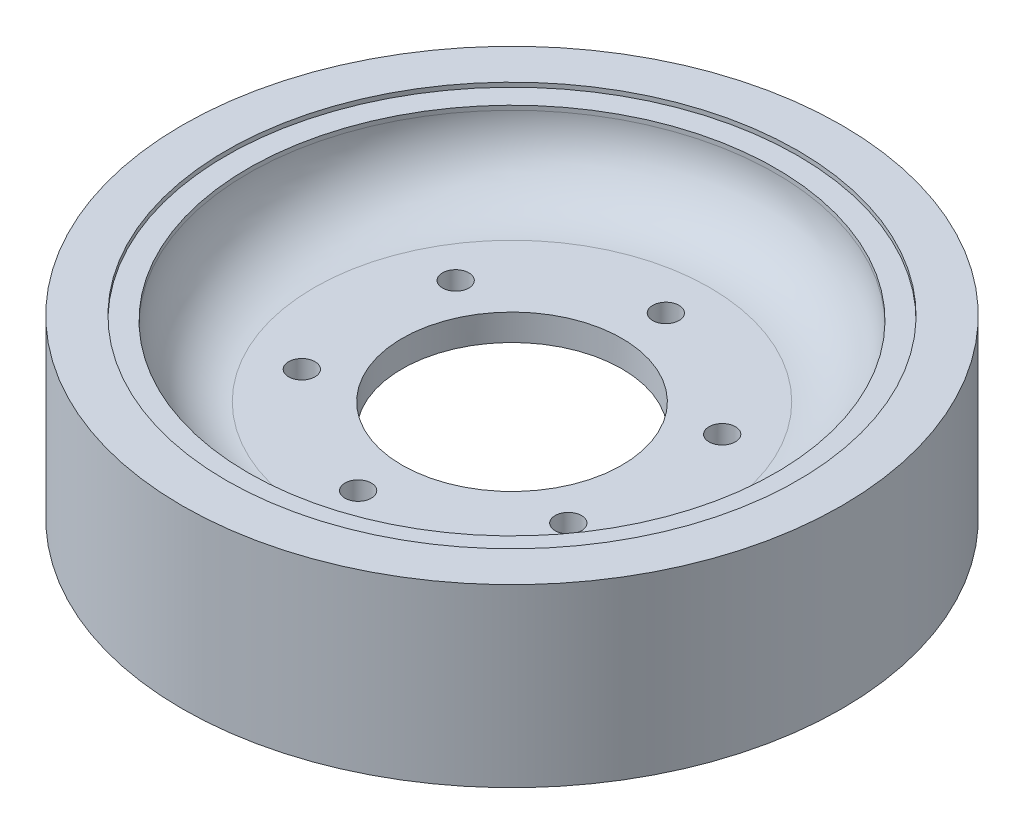
SolidWorks part; units mm, degrees
ref_plane "Front Plane" through (0, 0, 0) normal (0, 0, 1) x (1, 0, 0)
ref_plane "Top Plane" through (0, 0, 0) normal (0, 1, 0) x (1, 0, 0)
ref_plane "Right Plane" through (0, 0, 0) normal (1, 0, 0) x (0, 0, -1)
sketch "Sketch1" plane through (0, 0, 0) normal (0, 1, 0) x (1, 0, 0)
  circle A0 centre (0, 0) radius 75
  dimension "D1" = 150
extrude "Boss-Extrude1" add sketch "Sketch1" along normal blind 40
sketch "Sketch2" plane through (0, 40, 0) normal (0, 1, 0) x (1, 0, 0)
  circle A0 centre (0, 0) radius 60
  dimension "D1" = 120
extrude "Cut-Extrude1" cut sketch "Sketch2" against normal blind 17
sketch "Sketch3" plane through (0, 23, 0) normal (0, 1, 0) x (1, 0, 0)
  circle A0 centre (0, 0) radius 25
  dimension "D1" = 50
extrude "Cut-Extrude2" cut sketch "Sketch3" against normal through all
sketch "Sketch4" plane through (0, 23, 0) normal (0, 1, 0) x (1, 0, 0)
  circle A0 centre (0, 0) radius 35 construction
  circle A1 centre (0, 35) radius 3
  circle A2 centre (30.3109, 17.5) radius 3
  circle A3 centre (30.3109, -17.5) radius 3
  circle A4 centre (0, -35) radius 3
  circle A5 centre (-30.3109, -17.5) radius 3
  circle A6 centre (-30.3109, 17.5) radius 3
  point P17 (0, 0)
  dimension "D1" = 70
  dimension "D2" = 6
  dimension "D3" = 6
extrude "Cut-Extrude3" cut sketch "Sketch4" against normal through all
sketch "Sketch6" plane through (0, 0, 0) normal (0, -1, 0) x (1, 0, 0)
  circle A0 centre (0, 0) radius 60
  dimension "D1" = 120
extrude "Cut-Extrude4" cut sketch "Sketch6" against normal blind 17
sketch "Sketch7" plane through (0, 0, 0) normal (0, -1, 0) x (1, 0, 0)
  circle A0 centre (0, 0) radius 65
  dimension "D1" = 130
extrude "Cut-Extrude5" cut sketch "Sketch7" against normal blind 1
sketch "Sketch8" plane through (0, 40, 0) normal (0, 1, 0) x (1, 0, 0)
  circle A0 centre (0, 0) radius 65
  dimension "D1" = 130
extrude "Cut-Extrude6" cut sketch "Sketch8" against normal blind 1
fillet "Fillet1" radius 15 1 edges at (0, 23, 60)
fillet "Fillet2" radius 15 1 edges at (0, 17, -60)
